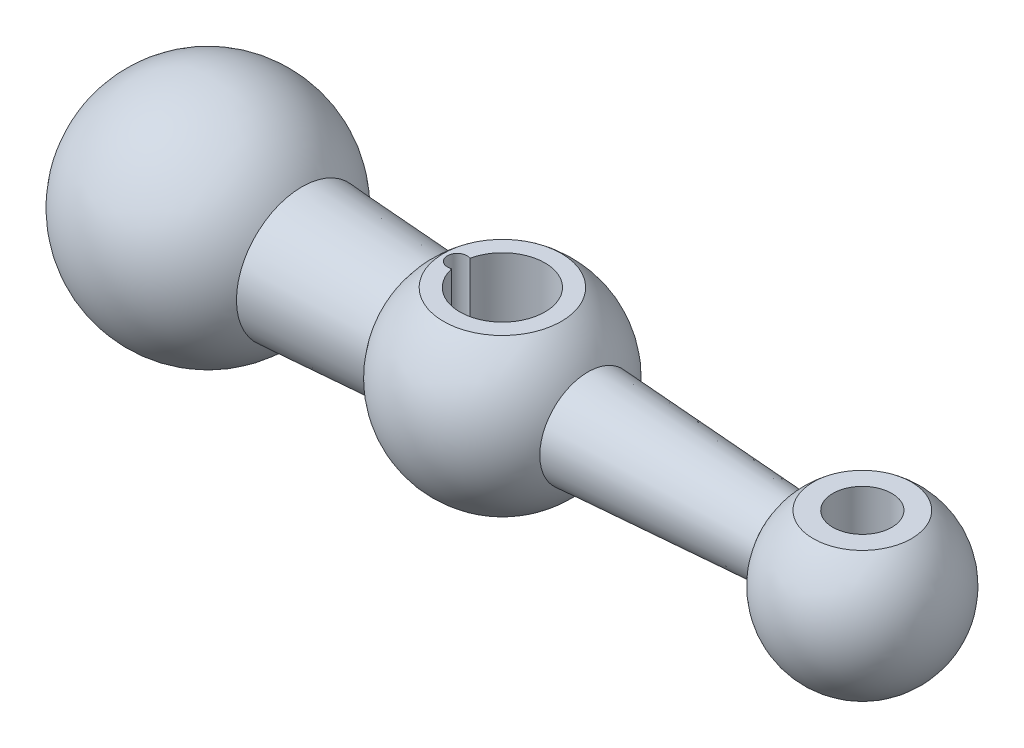
SolidWorks part; units mm, degrees
material "Cast Alloy Steel"
ref_plane "Front Plane" through (0, 0, 0) normal (0, 0, 1) x (1, 0, 0)
ref_plane "Top Plane" through (0, 0, 0) normal (0, 1, 0) x (1, 0, 0)
ref_plane "Right Plane" through (0, 0, 0) normal (1, 0, 0) x (0, 0, -1)
sketch "Sketch1" plane through (0, 0, 0) normal (0, 0, 1) x (1, 0, 0)
  line L0 (-17.5, 0) -> (112.5, 0) construction
  line L1 (14.3614, 10) -> (88.775, 5.5)
  circle A0 centre (0, 0) radius 17.5
  circle A1 centre (45, 0) radius 15
  circle A2 centre (100, 0) radius 12.5
  dimension "D1" = 35
  dimension "D2" = 30
  dimension "D3" = 45
  dimension "D4" = 25
  dimension "D5" = 55
  dimension "D6" = 20
  dimension "D7" = 11
revolve "Revolve1" add sketch "Sketch1" angle 360 about L0 region at (0, 7.4272, 0) region at (23.6078, 5.0443, 0) region at (44.6518, 3.9647, 0) region at (45.6605, 10.9217, 0) region at (73.0069, 3.2901, 0) region at (100, 5.3052, 0)
ref_plane "Plane1" through (0, 10, 0) normal (0, 1, 0) x (1, 0, 0)
sketch "Sketch2" plane through (0, 10, 0) normal (0, 1, 0) x (1, 0, 0)
  circle A0 centre (100, 0) radius 14.8924
extrude "Cut-Extrude1" cut sketch "Sketch2" along normal blind 10
hole_wizard "M10x1.0 Tapped Hole1" positions "Sketch3" profile "Sketch4" tap size "M10x1.0" standard "ANSI Metric"
sketch "Sketch3" plane through (0, 10, 0) normal (0, 1, 0) x (1, 0, 0)
  point P0 (100, 0)
sketch "Sketch4" plane through (100, 10, 0) normal (1, 0, 0) x (0, 0, 1)
  line L0 (0, 0) -> (0, 19)
  line L1 (0, 19) -> (4.5, 19)
  line L2 (4.5, 19) -> (4.5, 0)
  line L5 (4.5, 0) -> (0, 0)
  line L10 (0, 19) -> (-4.5, 19) construction
  line L11 (0, -6.35) -> (0, 107.95) construction
  dimension "Tap Drill Dia." = 9
  dimension "Tap Drill Depth" = 19
  dimension "Drill Angle" = 180
cosmetic thread "Hole Thread1" parameters "D1"=16, "D2"=10
sketch "Sketch5" plane through (0, 0, 0) normal (0, 0, 1) x (1, 0, 0)
  line L0 (0, 0) -> (75.6296, 0) construction
  line L1 (28.1659, 15.4028) -> (62.0183, 15.4028)
  line L2 (28.1659, 15.4028) -> (28.1659, 12)
  line L3 (28.1659, 12) -> (62.0183, 12)
  line L4 (62.0183, 15.4028) -> (62.0183, 12)
  line L5 (28.1659, -15.7269) -> (62.0183, -15.7269)
  line L6 (28.1659, -15.7269) -> (28.1659, -12)
  line L7 (28.1659, -12) -> (62.0183, -12)
  line L8 (62.0183, -15.7269) -> (62.0183, -12)
  dimension "D1" = 24
extrude "Cut-Extrude2" cut sketch "Sketch5" against normal through all both and the other way through all
sketch "Sketch6" plane through (0, 12, 0) normal (0, 1, 0) x (1, 0, 0)
  circle A0 centre (45, 0) radius 6.5
  circle A1 centre (45, 0) radius 9 construction
  dimension "D1" = 13
extrude "Cut-Extrude3" cut sketch "Sketch6" against normal through all both and the other way through all
sketch "Sketch7" plane through (0, 12, 0) normal (0, 1, 0) x (1, 0, 0)
  circle A0 centre (38.1035, 0) radius 1.5
  circle A1 centre (45, 0) radius 6.5 construction
  point P2 (38.1035, 0)
  dimension "D1" = 3
  dimension "D2" = 6.8965
extrude "Cut-Extrude5" cut sketch "Sketch7" against normal blind 12 contours A0
